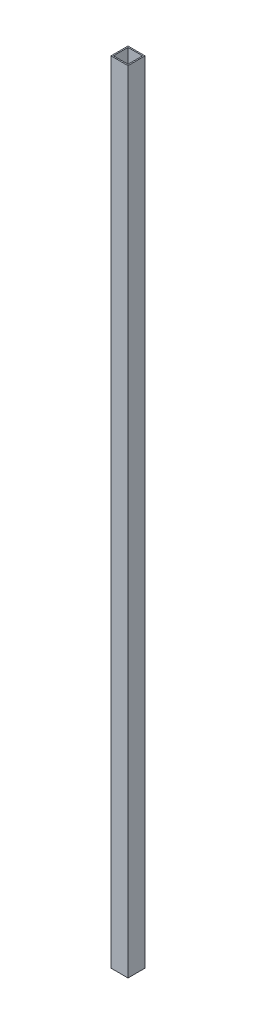
SolidWorks part; units mm, degrees
ref_plane "Спереди" through (0, 0, 0) normal (0, 0, 1) x (1, 0, 0)
ref_plane "Сверху" through (0, 0, 0) normal (0, 1, 0) x (1, 0, 0)
ref_plane "Справа" through (0, 0, 0) normal (1, 0, 0) x (0, 0, -1)
sketch "Эскиз1" plane through (0, 0, 0) normal (0, 1, 0) x (1, 0, 0)
  line L1 (-6, 6) -> (6, 6)
  line L2 (-6, 6) -> (-6, -6)
  line L3 (-6, -6) -> (6, -6)
  line L4 (6, 6) -> (6, -6)
  line L5 (-6, 6) -> (6, -6) construction
  line L6 (-6, -6) -> (6, 6) construction
  line L7 (-7, 7) -> (7, 7)
  line L8 (-7, 7) -> (-7, -7)
  line L9 (-7, -7) -> (7, -7)
  line L10 (7, 7) -> (7, -7)
  line L11 (-7, 7) -> (7, -7) construction
  line L12 (-7, -7) -> (7, 7) construction
  point P0 (0, 0)
  point P6 (0, 0)
  point P11 (-7, 0)
  dimension "D1" = 14
  dimension "D2" = 14
  dimension "D3" = 1
  dimension "D4" = 1
extrude "Бобышка-Вытянуть1" add sketch "Эскиз1" along normal blind 650
